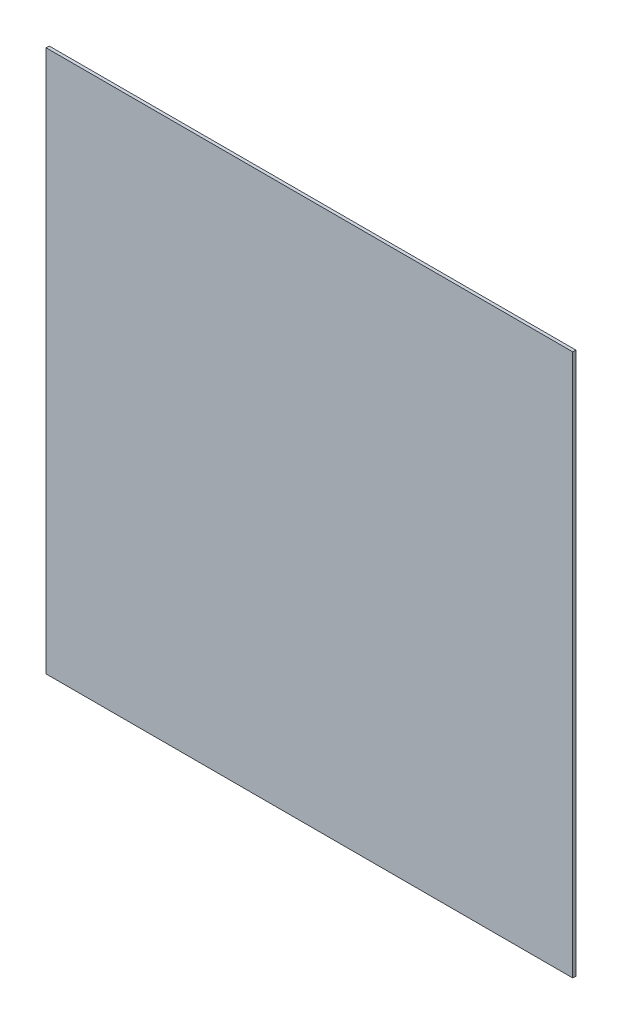
SolidWorks part; units mm, degrees
ref_plane "Přední rovina" through (0, 0, 0) normal (0, 0, 1) x (1, 0, 0)
ref_plane "Horní rovina" through (0, 0, 0) normal (0, 1, 0) x (1, 0, 0)
ref_plane "Pravá rovina" through (0, 0, 0) normal (1, 0, 0) x (0, 0, -1)
sketch "Skica1" plane through (0, 0, 0) normal (0, 0, 1) x (1, 0, 0)
  line L1 (-252.5, 260) -> (252.5, 260)
  line L2 (-252.5, 260) -> (-252.5, -260)
  line L3 (-252.5, -260) -> (252.5, -260)
  line L4 (252.5, 260) -> (252.5, -260)
  line L5 (-252.5, 260) -> (252.5, -260) construction
  line L6 (-252.5, -260) -> (252.5, 260) construction
  point P0 (0, 0)
  dimension "D1" = 505
  dimension "D2" = 520
extrude "Přidat vysunutím1" add sketch "Skica1" along normal blind 3
